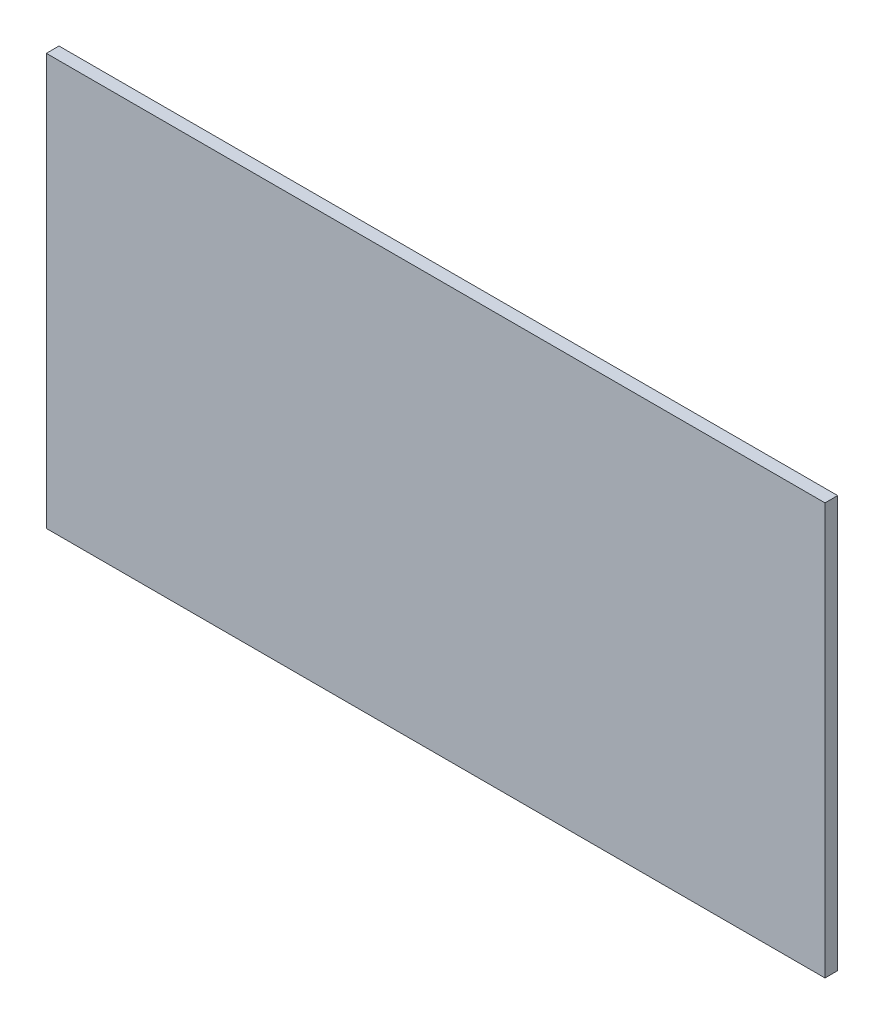
SolidWorks part; units mm, degrees
ref_plane "Front" through (0, 0, 0) normal (0, 0, 1) x (1, 0, 0)
ref_plane "Top" through (0, 0, 0) normal (0, 1, 0) x (1, 0, 0)
ref_plane "Right" through (0, 0, 0) normal (1, 0, 0) x (0, 0, -1)
sketch "Эскиз1" plane through (0, 0, 0) normal (0, 0, 1) x (1, 0, 0)
  line L1 (115.5, 243) -> (484.5, 243)
  line L2 (115.5, 243) -> (115.5, 48)
  line L3 (115.5, 48) -> (484.5, 48)
  line L4 (484.5, 243) -> (484.5, 48)
  dimension "D1" = 369
  dimension "D2" = 195
extrude "Бобышка-Вытянуть1" add sketch "Эскиз1" along normal blind 6
